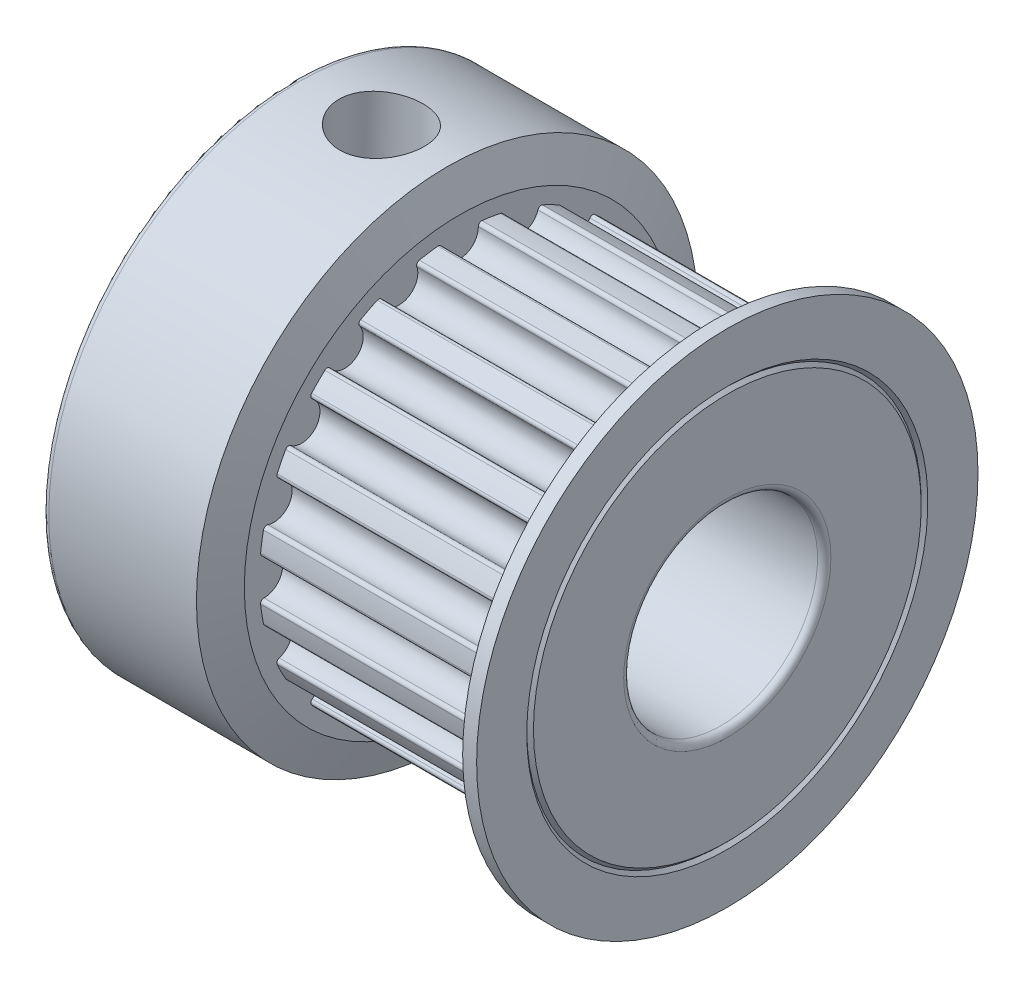
SolidWorks part; units mm, degrees
material "Alumina"
ref_plane "Front" through (0, 0, 0) normal (0, 0, 1) x (1, 0, 0)
ref_plane "Top" through (0, 0, 0) normal (0, 1, 0) x (1, 0, 0)
ref_plane "Right" through (0, 0, 0) normal (1, 0, 0) x (0, 0, -1)
sketch "Sketch 1" plane through (0, 0, 0) normal (0, 0, 1) x (1, 0, 0)
  line L0 (1, 2.9) -> (1, 7.5)
  line L1 (1, 0) -> (14, 0) construction
  line L2 (1, 7.5) -> (5.6176, 7.5)
  line L3 (5.6176, 7.5) -> (6, 6.4494)
  line L4 (6, 6) -> (13.2, 6)
  line L5 (13.2, 6) -> (13.2, 6.4494)
  line L6 (13.5824, 7.5) -> (14, 7.5)
  line L7 (14, 2.9) -> (14, 5.8)
  line L8 (14, 5.8) -> (13.9, 5.9)
  line L9 (13.9, 5.9) -> (14, 6)
  line L10 (14, 6) -> (14, 7.5)
  line L11 (14, 2.9) -> (1, 2.9)
  line L12 (6, 6.4494) -> (6, 6)
  line L13 (13.2, 6.4494) -> (13.5824, 7.5)
  dimension "D1" = 5
  dimension "D2" = 20
  dimension "D5" = 0.1
  dimension "D8" = 7.2
revolve "Body" add sketch "Sketch 1" angle 360 about L1 region at (7.0145, 4.8392, 0)
sketch "Sketch 3" plane through (6, 0, 0) normal (1, 0, 0) x (0, 0, -1)
  line L0 (0, 0) -> (9.7637, 0) construction
  circle A18 centre (0, 5.855) radius 0.55
  point P45 (0, 0)
extrude "Cut-Extrude1" cut sketch "Sketch 3" along normal up to surface (7.2 mm away) up to face at (13.2, 0, 6.4494)
fillet "Fillet" radius 0.1 2 edges at (9.6, 5.976, -0.5365) (9.6, 5.976, 0.5365)
ref_axis "Axis1" through (0.35, 0, 0) along (1, 0, 0)
pattern_circular "CirPattern1" count 20 over 360 about axis through (0.35, 0, 0) along (1, 0, 0) of "Cut-Extrude1", "Fillet"
hole_wizard "M3 Tapped Hole1" positions "3DSketch1" profile "Sketch1" tap size "M3" standard "DIN"
sketch3d "3DSketch1"
  point P0 (3.5, 7.4984, -0.1544)
  dimension "D1" = 2.5
sketch "Sketch1" plane through (3.5, 7.4984, -0.1544) normal (1, 0, 0) x (0, 0.0206, 0.9998)
  line L0 (0, 0) -> (0, 8.2511)
  line L1 (0, 8.2511) -> (1.25, 7.5)
  line L2 (1.25, 7.5) -> (1.25, 0)
  line L5 (1.25, 0) -> (0, 0)
  line L10 (0, 8.2511) -> (-1.25, 7.5) construction
  line L11 (0, -6.35) -> (0, 107.95) construction
  dimension "Tap Drill Dia." = 2.5
  dimension "Tap Drill Depth" = 7.5
  dimension "Drill Angle" = 118
cosmetic thread "Hole Thread1" parameters "D1"=4.8832, "D2"=3
fillet "Fillet1" radius 0.2 4 edges at (14, 0, 2.9) (1, 0, 2.9) (3.6689, 2.5962, -1.2922) (1, 0, 7.5)
